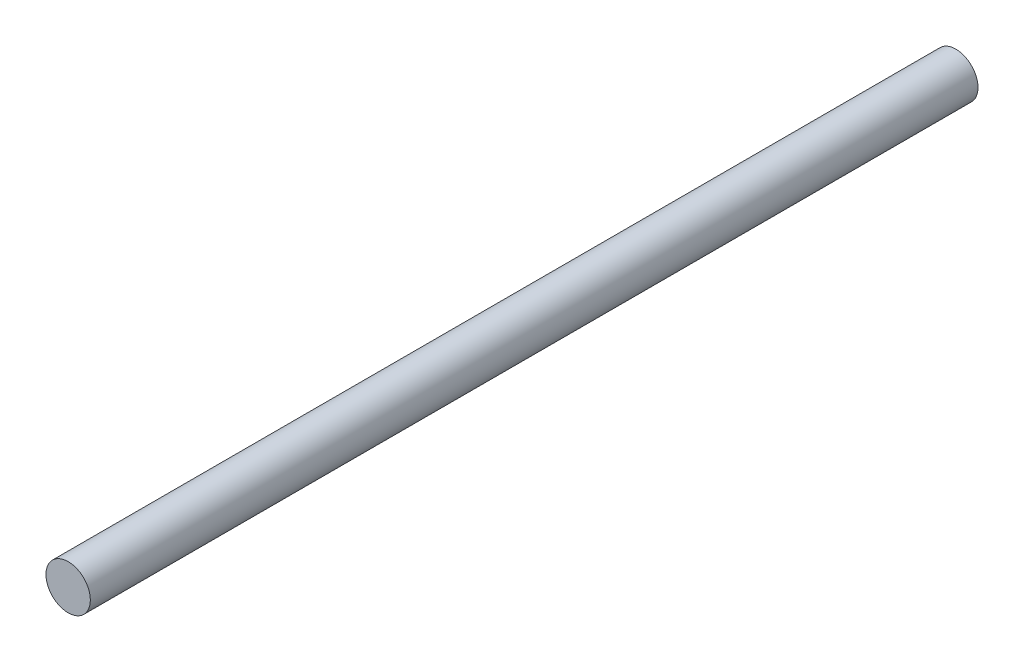
SolidWorks part; units mm, degrees
ref_plane "前视基准面" through (0, 0, 0) normal (0, 0, 1) x (1, 0, 0)
ref_plane "上视基准面" through (0, 0, 0) normal (0, 1, 0) x (1, 0, 0)
ref_plane "右视基准面" through (0, 0, 0) normal (1, 0, 0) x (0, 0, -1)
sketch "草图1" plane through (0, 0, 0) normal (0, 0, 1) x (1, 0, 0)
  circle A0 centre (0, 0) radius 1.5
extrude "凸台-拉伸1" add sketch "草图1" along normal blind 60
ref_axis "基准轴1" through (0, 0, 60) along (0, 0, -1)
